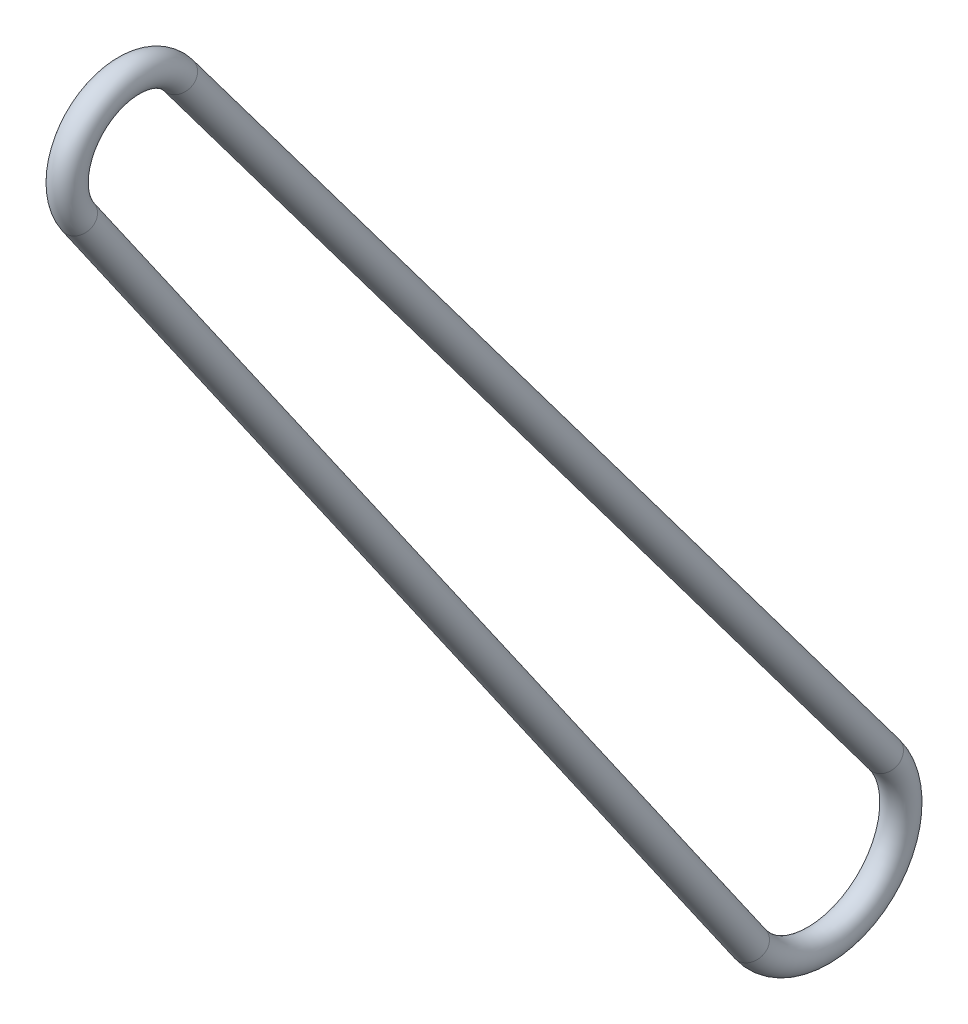
SolidWorks part; units mm, degrees
ref_plane "Front" through (0, 0, 0) normal (0, 0, 1) x (1, 0, 0)
ref_plane "Top" through (0, 0, 0) normal (0, 1, 0) x (1, 0, 0)
ref_plane "Right" through (0, 0, 0) normal (1, 0, 0) x (0, 0, -1)
ref_axis "side-side" through (80.9, 0, 0) along (-1, 0, 0)
ref_axis "up-down" through (0, 50, 0) along (0, -1, 0)
ref_axis "front-back" through (0, 0, -80.9) along (0, 0, 1)
sketch "Sketch1" plane through (0, 0, 0) normal (1, 0, 0) x (0, 0, -1)
  line L0 (100.3497, -120.0697) -> (6.5755, 4.9328)
  line L1 (82.522, -132.9545) -> (-6.7468, -4.6958)
  arc A0 (6.5755, 4.9328) -> (-6.7468, -4.6958) centre (0, 0) ccw
  circle A1 centre (91.5505, -126.6707) radius 11 construction
  arc A2 (82.522, -132.9545) -> (100.3497, -120.0697) centre (91.5505, -126.6707) ccw
  dimension "D1" = 156.2665
ref_plane "Plane1" through (0, 4.9328, -6.5755) normal (0, 0.7999, 0.6001) x (1, 0, 0)
sketch "Sketch2" plane through (0, 4.9328, -6.5755) normal (0, 0.7999, 0.6001) x (1, 0, 0)
  circle A0 centre (0, 0) radius 1.9844
  dimension "D1" = 3.9688
sweep "Sweep1" add profiles "Sketch2" path "Sketch1"
sketch "Sketch3" plane through (0, 0, 0) normal (1, 0, 0) x (0, 0, -1)
  line L0 (-5.1181, -3.5622) -> (84.1507, -131.8209)
  line L1 (80.8933, -134.0881) -> (-8.3755, -5.8294)
  line L2 (80.8933, -134.0881) -> (-8.3755, -5.8294)
  line L3 (-5.1181, -3.5622) -> (84.1507, -131.8209)
  line L4 (98.7624, -121.2605) -> (4.9881, 3.742)
  line L5 (8.1629, 6.1236) -> (101.9371, -118.8788)
  line L6 (8.1629, 6.1236) -> (101.9371, -118.8788)
  line L7 (98.7624, -121.2605) -> (4.9881, 3.742)
  arc A0 (80.8933, -134.0881) -> (101.9371, -118.8788) centre (91.5505, -126.6707) ccw
  arc A1 (84.1507, -131.8209) -> (98.7624, -121.2605) centre (91.5505, -126.6707) ccw
  arc A2 (84.1507, -131.8209) -> (98.7624, -121.2605) centre (91.5505, -126.6707) ccw
  arc A3 (80.8933, -134.0881) -> (101.9371, -118.8788) centre (91.5505, -126.6707) ccw
  arc A4 (8.1629, 6.1236) -> (-8.3755, -5.8294) centre (0, 0) ccw
  arc A5 (4.9881, 3.742) -> (-5.1181, -3.5622) centre (0, 0) ccw
  arc A6 (4.9881, 3.742) -> (-5.1181, -3.5622) centre (0, 0) ccw
  arc A7 (8.1629, 6.1236) -> (-8.3755, -5.8294) centre (0, 0) ccw
